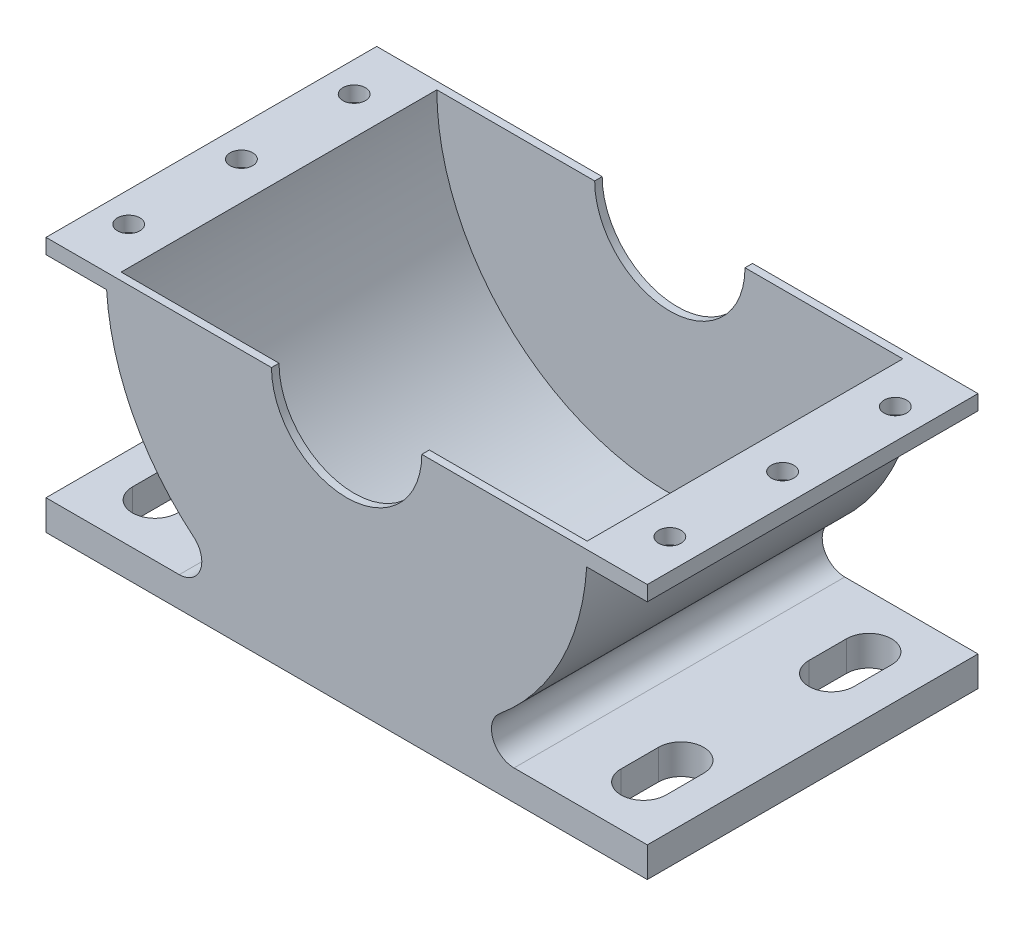
SolidWorks part; units mm, degrees
ref_plane "Front Plane" through (0, 0, 0) normal (0, 0, 1) x (1, 0, 0)
ref_plane "Top Plane" through (0, 0, 0) normal (0, 1, 0) x (1, 0, 0)
ref_plane "Right Plane" through (0, 0, 0) normal (1, 0, 0) x (0, 0, -1)
sketch "Sketch1" plane through (0, 0, 0) normal (0, 0, 1) x (1, 0, 0)
  line L0 (0, 0) -> (-40, 0)
  line L1 (-40, 0) -> (-40, 4)
  line L2 (-40, 4) -> (-11.1355, 4)
  line L3 (-40, 34) -> (0, 34)
  line L4 (0, 34) -> (0, 0)
  line L5 (-40, 34) -> (-40, 32)
  line L6 (-40, 32) -> (-31.9374, 32)
  arc A2 (-31.9374, 32) -> (-11.1355, 4) centre (0, 34) ccw
  arc A3 (-31.9374, 32) -> (-32, 34) centre (0, 34) cw
  arc A4 (-11.1355, 4) -> (0, 2) centre (0, 34) ccw
  dimension "D4" = 32
  dimension "D1" = 34
  dimension "D2" = 4
  dimension "D3" = 2
  dimension "D5" = 40
extrude "Boss-Extrude1" add sketch "Sketch1" along normal mid plane 44 contours A3 A2 L2 L1 L0 L4 L3 region at (-13.5812, 20.4188, 0)
mirror "Mirror1" about plane through (0, 0, 22) normal (1, 0, 0) of bodies 101
shell "Shell1" thickness 1 removed face at (0, 34, 0)
extrude "Boss-Extrude2" add sketch "Sketch1<3>" along normal mid plane 44 contours L6 A3 L3 L5 region at (-35.9896, 32.9987, 0)
sketch "Sketch1<3>" plane through (0, 0, 0) normal (0, 0, 1) x (1, 0, 0) same geometry as "Sketch1"
extrude "Boss-Extrude3" add sketch "Sketch1<4>" along normal mid plane 44 contours A4 L2 L1 L0 L4 region at (-21.6282, 1.8766, 0)
sketch "Sketch1<4>" plane through (0, 0, 0) normal (0, 0, 1) x (1, 0, 0) same geometry as "Sketch1"
mirror "Mirror2" about plane through (0, 0, 0) normal (1, 0, 0) of "Boss-Extrude3"
mirror "Mirror4" about plane through (0, 0, 0) normal (1, 0, 0) of "Boss-Extrude2"
fillet "Fillet2" radius 3 2 edges at (11.1355, 4, 0) (-11.1355, 4, 0)
sketch "Sketch2" plane through (0, 34, 0) normal (0, 1, 0) x (1, 0, 0)
  line L0 (-36, 22) -> (-36, -22) construction
  line L1 (-40, 22) -> (40, 22) construction
  line L2 (-40, -22) -> (40, -22) construction
  line L3 (0, 0) -> (0, 22) construction
  circle A0 centre (-36, 15) radius 1.5
  circle A1 centre (-36, 0) radius 1.5
  circle A2 centre (-36, -15) radius 1.5
  circle A3 centre (36, -15) radius 1.5
  circle A4 centre (36, 0) radius 1.5
  circle A5 centre (36, 15) radius 1.5
  dimension "D1" = 3
  dimension "D2" = 30
  dimension "D3" = 15
  dimension "D4" = 36
extrude "Cut-Extrude1" cut sketch "Sketch2" against normal up to next
sketch "Sketch3" plane through (0, 0, 0) normal (0, -1, 0) x (1, 0, 0)
  line L0 (0, 22) -> (0, 0) construction
  line L1 (40, 22) -> (-40, 22) construction
  line L2 (-32.5, 15) -> (-32.5, 10) construction
  line L3 (-29.5, 15) -> (-29.5, 10)
  line L4 (-35.5, 15) -> (-35.5, 10)
  line L5 (-32.5, -10) -> (-32.5, -15) construction
  line L6 (-29.5, -10) -> (-29.5, -15)
  line L7 (-35.5, -10) -> (-35.5, -15)
  line L8 (32.5, -10) -> (32.5, -15) construction
  line L9 (29.5, -10) -> (29.5, -15)
  line L10 (35.5, -10) -> (35.5, -15)
  line L11 (32.5, 15) -> (32.5, 10) construction
  line L12 (29.5, 15) -> (29.5, 10)
  line L13 (35.5, 15) -> (35.5, 10)
  arc A0 (-29.5, 15) -> (-35.5, 15) centre (-32.5, 15) ccw
  arc A1 (-35.5, 10) -> (-29.5, 10) centre (-32.5, 10) ccw
  arc A2 (-29.5, -10) -> (-35.5, -10) centre (-32.5, -10) ccw
  arc A3 (-35.5, -15) -> (-29.5, -15) centre (-32.5, -15) ccw
  arc A4 (29.5, -10) -> (35.5, -10) centre (32.5, -10) cw
  arc A5 (35.5, -15) -> (29.5, -15) centre (32.5, -15) cw
  arc A6 (29.5, 15) -> (35.5, 15) centre (32.5, 15) cw
  arc A7 (35.5, 10) -> (29.5, 10) centre (32.5, 10) cw
  point P7 (-32.5, 12.5)
  point P14 (-32.5, -12.5)
  point P21 (32.5, -12.5)
  point P28 (32.5, 12.5)
  dimension "D1" = 3
  dimension "D2" = 5
  dimension "D3" = 5
  dimension "D4" = 25
  dimension "D5" = 12.5
  dimension "D6" = 32.5
extrude "Cut-Extrude2" cut sketch "Sketch3" against normal up to next
sketch "Sketch4" plane through (0, 0, 22) normal (0, 0, 1) x (1, 0, 0)
  line L0 (-40, 34) -> (40, 34) construction
  circle A0 centre (0, 34) radius 10
  dimension "D1" = 20
extrude "Cut-Extrude3" cut sketch "Sketch4" against normal up to surface (44 mm away) up to face at (0, 16.206, -22)
